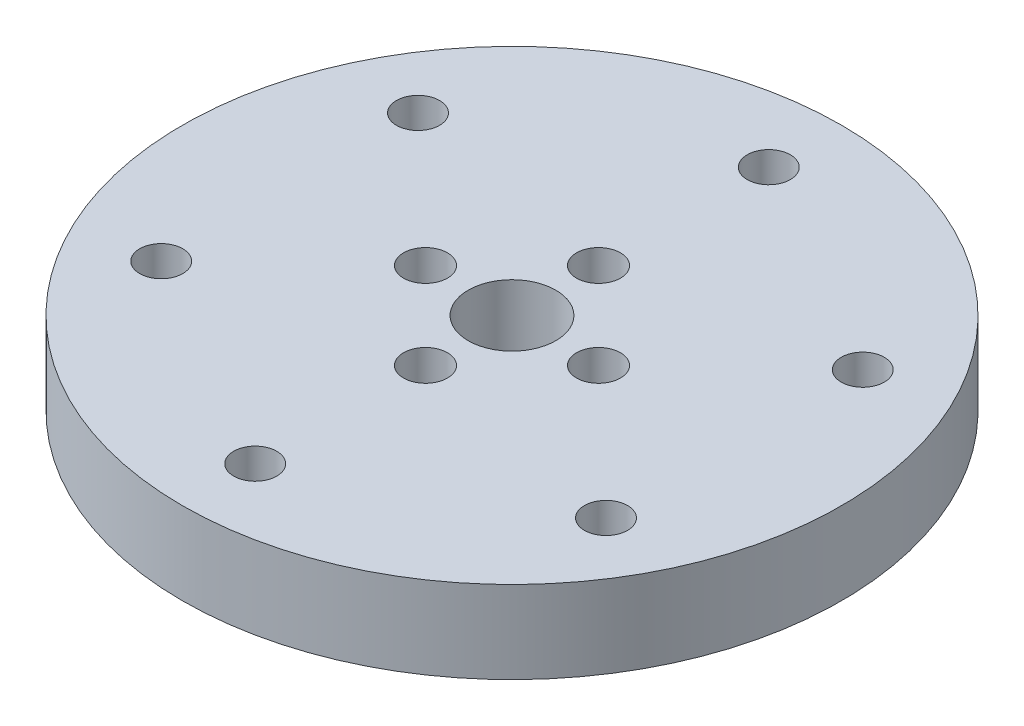
SolidWorks part; units mm, degrees
ref_plane "Front Plane" through (0, 0, 0) normal (0, 0, 1) x (1, 0, 0)
ref_plane "Top Plane" through (0, 0, 0) normal (0, 1, 0) x (1, 0, 0)
ref_plane "Right Plane" through (0, 0, 0) normal (1, 0, 0) x (0, 0, -1)
sketch "Sketch1" plane through (0, 0, 0) normal (0, 1, 0) x (1, 0, 0)
  circle A0 centre (0, 0) radius 30.48
  dimension "D1" = 60.96
extrude "Boss-Extrude1" add sketch "Sketch1" along normal blind 7.62 contours A0
sketch "Sketch2" plane through (0, 7.62, 0) normal (0, 1, 0) x (1, 0, 0)
  line L0 (0, 0) -> (0, -23.749)
  circle A0 centre (0, 0) radius 23.749
  circle A1 centre (0, -23.749) radius 1.9939
  dimension "D1" = 47.498
  dimension "D2" = 3.9878
extrude "Cut-Extrude1" cut sketch "Sketch2" against normal through all contours A1
pattern_circular "CirPattern1" count 6 over 360 about axis through (0, 7.62, 0) along (0, -1, 0) of "Cut-Extrude1"
sketch "Sketch3" plane through (0, 7.62, 0) normal (0, 1, 0) x (1, 0, 0)
  circle A0 centre (0, 0) radius 4.0513
  circle A2 centre (0, -8.001) radius 2.032
  dimension "D1" = 8.1026
  dimension "D3" = 4.064
extrude "Cut-Extrude2" cut sketch "Sketch3" against normal through all contours A0 | A2
pattern_circular "CirPattern2" count 4 over 360 about axis through (0, 7.62, 0) along (0, -1, 0) of "Cut-Extrude2"
